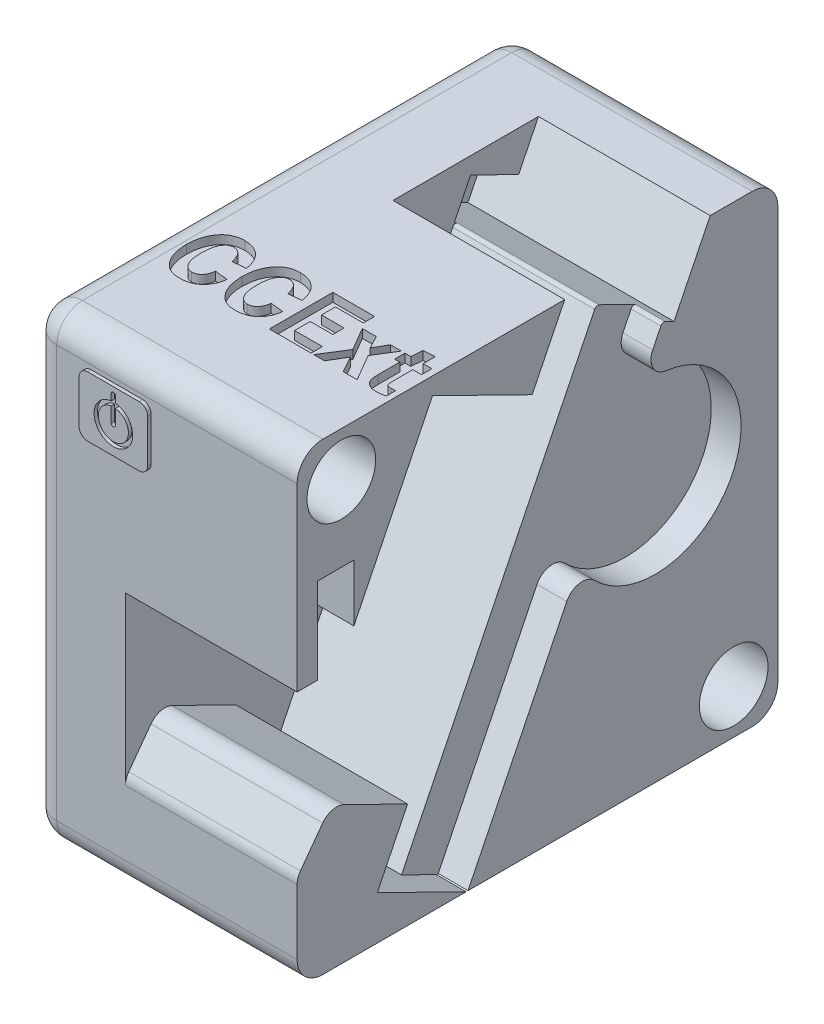
SolidWorks part; units mm, degrees
material "ABS"
ref_plane "Front" through (0, 0, 0) normal (0, 0, 1) x (1, 0, 0)
ref_plane "Top" through (0, 0, 0) normal (0, 1, 0) x (1, 0, 0)
ref_plane "Right" through (0, 0, 0) normal (1, 0, 0) x (0, 0, -1)
sketch "Sketch1" plane through (0, 0, 0) normal (0, 0, 1) x (1, 0, 0)
  line L0 (133.4483, 300.2587) -> (667.2416, 300.2587) construction
  line L2 (-196.85, 342.9) -> (196.85, 342.9)
  line L3 (-196.85, 342.9) -> (-196.85, 0)
  line L4 (-196.85, 0) -> (196.85, 0)
  line L5 (196.85, 342.9) -> (196.85, 0)
  dimension "D1" = 342.9
  dimension "D2" = 393.7
extrude "Boss-Extrude1" add sketch "Sketch1" along normal blind 355.6
sketch "Sketch2" plane through (0, 0, 355.6) normal (0, 0, 1) x (1, 0, 0)
  line L0 (196.85, 342.9) -> (-196.85, 342.9) construction
  line L1 (-158.75, 320.675) -> (-107.95, 320.675)
  line L2 (-158.75, 320.675) -> (-158.75, 276.225)
  line L3 (-158.75, 276.225) -> (-107.95, 276.225)
  line L4 (-107.95, 320.675) -> (-107.95, 276.225)
  line L5 (-158.75, 320.675) -> (-107.95, 276.225) construction
  line L6 (-158.75, 276.225) -> (-107.95, 320.675) construction
  line L7 (-196.85, 342.9) -> (-196.85, 0) construction
  point P0 (-133.35, 298.45)
  dimension "D1" = 44.45
  dimension "D2" = 63.5
  dimension "D3" = 44.45
  dimension "D4" = 50.8
extrude "Boss-Extrude2" add sketch "Sketch2" along normal blind 2.54
sketch "Sketch3" plane through (0, 0, 355.6) normal (0, 0, 1) x (1, 0, 0)
  line L0 (88.9, 298.45) -> (165.1, 298.45) construction
  line L1 (88.9, 307.975) -> (165.1, 307.975)
  line L2 (88.9, 288.925) -> (165.1, 288.925)
  line L5 (-107.95, 298.45) -> (88.9, 298.45) construction
  line L7 (-107.95, 276.225) -> (-107.95, 320.675) construction
  line L8 (196.85, 0) -> (196.85, 342.9) construction
  arc A0 (88.9, 307.975) -> (88.9, 288.925) centre (88.9, 298.45) ccw
  arc A1 (165.1, 288.925) -> (165.1, 307.975) centre (165.1, 298.45) ccw
  point P2 (127, 298.45)
  dimension "D1" = 19.05
  dimension "D2" = 76.2
  dimension "D3" = 31.75
extrude "Boss-Extrude3" add sketch "Sketch3" along normal blind 2.54
sketch "Sketch4" plane through (0, 0, 358.14) normal (0, 0, 1) x (1, 0, 0)
  line L0 (79.375, 298.45) -> (174.625, 298.45) construction
  arc A0 (88.9, 307.975) -> (88.9, 288.925) centre (88.9, 298.45) ccw construction
  arc A1 (165.1, 288.925) -> (165.1, 307.975) centre (165.1, 298.45) ccw construction
  circle A2 centre (92.075, 298.45) radius 3.81
  circle A3 centre (108.2865, 298.45) radius 3.81
  circle A4 centre (124.4979, 298.45) radius 3.81
  dimension "D1" = 7.62
  dimension "D2" = 16.2115
  dimension "D3" = 16.2115
  dimension "D4" = 12.7
extrude "Cut-Extrude1" cut sketch "Sketch4" against normal blind 2.54
sketch "Sketch5" plane through (0, 0, 355.6) normal (0, 0, 1) x (1, 0, 0)
  line L0 (-114.3, 177.8) -> (114.3, 177.8) construction
  line L1 (-114.3, 190.5) -> (114.3, 190.5)
  line L2 (-114.3, 165.1) -> (114.3, 165.1)
  line L3 (0, 177.8) -> (0, 342.9) construction
  line L4 (196.85, 342.9) -> (-196.85, 342.9) construction
  arc A0 (-114.3, 190.5) -> (-114.3, 165.1) centre (-114.3, 177.8) ccw
  arc A1 (114.3, 165.1) -> (114.3, 190.5) centre (114.3, 177.8) ccw
  point P2 (0, 177.8)
  dimension "D1" = 228.6
  dimension "D2" = 25.4
  dimension "D3" = 165.1
extrude "Boss-Extrude4" add sketch "Sketch5" along normal blind 50.8
fillet "Fillet1" radius 6.35 4 edges at (127, 177.8, 406.4) (0, 165.1, 406.4) (-127, 177.8, 406.4) (0, 190.5, 406.4)
fillet "Fillet2" radius 6.35 4 edges at (-158.75, 276.225, 356.87) (-107.95, 276.225, 356.87) (-107.95, 320.675, 356.87) (-158.75, 320.675, 356.87)
sketch "Sketch6" plane through (0, 0, 358.14) normal (0, 0, 1) x (1, 0, 0)
  line L0 (-133.35, 296.545) -> (-133.35, 276.225) construction
  line L3 (-133.35, 296.545) -> (-133.35, 315.595) construction
  line L4 (-134.9375, 296.545) -> (-134.9375, 315.595)
  line L5 (-131.7625, 296.545) -> (-131.7625, 315.595)
  line L6 (-152.4, 276.225) -> (-114.3, 276.225) construction
  circle A1 centre (-133.35, 296.545) radius 11.1125
  circle A2 centre (-133.35, 296.545) radius 14.2875
  arc A3 (-134.9375, 296.545) -> (-131.7625, 296.545) centre (-133.35, 296.545) ccw
  arc A4 (-131.7625, 315.595) -> (-134.9375, 315.595) centre (-133.35, 315.595) ccw
  point P12 (-133.35, 306.07)
  dimension "D2" = 22.225
  dimension "D3" = 3.175
  dimension "D4" = 19.05
  dimension "D5" = 20.32
  dimension "D1" = 3.175
extrude "Cut-Extrude2" cut sketch "Sketch6" against normal blind 2.54 contours L4 A2 L5 A1 | L5 A4 L4 A2 | L5 A2 L4 A1 | L4 A3 L5 A1 region at (-133.35, 301.4538, 358.14) region at (-140.889, 287.8397, 358.14) region at (-133.35, 309.2112, 358.14) region at (-133.35, 313.8328, 358.14)
fillet "Fillet3" radius 19.05 12 edges at (-196.85, 171.45, 0) (-196.85, 171.45, 355.6) (196.85, 171.45, 0) (196.85, 171.45, 355.6) (0, 0, 0) (0, 0, 355.6) (0, 342.9, 0) (0, 342.9, 355.6) (-196.85, 342.9, 177.8) (196.85, 0, 177.8) (-196.85, 0, 177.8) (196.85, 342.9, 177.8)
sketch "Sketch7" plane through (0, 0, 0) normal (1, 0, 0) x (0, 0, -1)
  line L0 (-51.7276, 342.9) -> (10.6627, 469.9)
  line L1 (-336.55, 342.9) -> (-19.05, 342.9) construction
  line L2 (-94.1768, 342.9) -> (-31.7865, 469.9)
  line L3 (-31.7865, 469.9) -> (10.6627, 469.9)
  line L4 (-94.1768, 342.9) -> (-51.7276, 342.9)
  line L5 (0, 323.85) -> (0, 19.05) construction
  dimension "D1" = 38.1
  dimension "D2" = 127
  dimension "D3" = 94.1768
  dimension "D4" = 63.837
extrude "Boss-Extrude5" add sketch "Sketch7" along normal mid plane 254
fillet "Fillet4" radius 39.116 2 edges at (-127, 469.9, 10.5619) (127, 469.9, 10.5619)
sketch "Sketch8" plane through (0, 342.9, 0) normal (0, 1, 0) x (1, 0, 0)
  line L0 (0, -94.1768) -> (0, -125.9268) construction
  line L1 (127, -94.1768) -> (-127, -94.1768) construction
  line L3 (-127, -157.6768) -> (127, -157.6768)
  line L4 (-127, -157.6768) -> (-127, -94.1768)
  line L5 (-127, -94.1768) -> (127, -94.1768)
  line L6 (127, -157.6768) -> (127, -94.1768)
  line L7 (-127, -157.6768) -> (127, -94.1768) construction
  line L8 (-127, -94.1768) -> (127, -157.6768) construction
  dimension "D1" = 63.5
  dimension "D2" = 254
extrude "Cut-Extrude3" cut sketch "Sketch8" against normal blind 25.4
sketch "Sketch9" plane through (0, 0, 0) normal (1, 0, 0) x (0, 0, -1)
  line L1 (-912.7094, 769.4471) -> (-210.006, -1175.153)
  line L2 (-210.006, -1175.153) -> (1122.7154, 405.706)
  line L3 (1122.7154, 405.706) -> (-912.7094, 769.4471)
  circle A0 centre (0, 0) radius 596.8851 construction
extrude "Cut-Extrude4" cut sketch "Sketch9" along normal through all
sketch "Sketch10" plane through (0, 0, 0) normal (1, 0, 0) x (0, 0, -1)
  line L0 (-94.1768, 342.9) -> (-256.3917, 12.7)
  line L1 (-157.6768, 342.9) -> (-181.7103, 293.9781)
  line L2 (-31.7865, 469.9) -> (-94.1768, 342.9) construction
  line L3 (-336.55, 165.1) -> (-255.4426, 330.2)
  line L5 (-355.6, 19.05) -> (-355.6, 165.1) construction
  line L9 (-157.6768, 342.9) -> (-94.1768, 342.9)
  line L14 (-255.4426, 330.2) -> (-181.7103, 293.9781)
  line L15 (-336.55, 0) -> (-19.05, 0) construction
  line L16 (-157.6768, 342.9) -> (-336.55, 342.9) construction
  line L17 (-341.781, 111.2476) -> (-273.8883, 77.8944)
  line L19 (-256.3917, 12.7) -> (-296.2874, 32.2993)
  line L20 (-296.2874, 32.2993) -> (-273.8883, 77.8944)
  line L21 (-336.55, 165.1) -> (-355.6, 165.1)
  line L22 (-355.6, 165.1) -> (-355.6, 83.1181)
  line L23 (-238.3444, 321.8003) -> (-409.5147, -26.6293) construction
  line L24 (-341.781, 111.2476) -> (-355.6, 83.1181)
  dimension "D1" = 12.7
  dimension "D2" = 12.7
  dimension "D3" = 50.8
  dimension "D4" = 44.45
  dimension "D5" = 19.05
  dimension "D6" = 19.05
extrude "Cut-Extrude5" cut sketch "Sketch10" against normal blind 127
sketch "Sketch11" plane through (0, 0, 0) normal (1, 0, 0) x (0, 0, -1)
  line L0 (-94.1768, 342.9) -> (-106.6549, 317.5)
  line L1 (-106.6549, 317.5) -> (-94.1768, 317.5)
  line L2 (-94.1768, 317.5) -> (-94.1768, 342.9)
extrude "Boss-Extrude6" add sketch "Sketch11" against normal up to surface (127 mm away) up to face at (-127, 199.4183, 238.9182)
sketch "Sketch12" plane through (0, 103.9367, 211.5706) normal (0, 0.4409, 0.8975) x (1, 0, 0)
  line L0 (-127, -101.6517) -> (0, -101.6517) construction
  line L1 (0, 426.4566) -> (-22, 426.4566)
  line L2 (0, 426.4566) -> (0, -101.6517)
  line L3 (0, -101.6517) -> (-22, -101.6517)
  line L4 (-22, 426.4566) -> (-22, -101.6517)
  dimension "D1" = 22
extrude "Cut-Extrude6" cut sketch "Sketch12" against normal blind 30
sketch "Sketch13" plane through (0, 0, 0) normal (1, 0, 0) x (0, 0, -1)
  line L0 (-90.7362, 196.8695) -> (0, 196.8695) construction
  line L1 (0, 19.05) -> (0, 323.85) construction
  line L2 (-90.7362, 196.8695) -> (-90.7362, 0) construction
  line L3 (-336.55, 0) -> (-230.5399, 0) construction
  circle A0 centre (-90.7362, 196.8695) radius 63.5
  dimension "D3" = 127
  dimension "D1" = 196.8695
  dimension "D2" = 90.7362
extrude "Cut-Extrude7" cut sketch "Sketch13" against normal up to surface (22 mm away) up to face at (-22, 190.5, 149.2572)
fillet "Fillet5" radius 12.7 2 edges at (-11, 259.4033, 101.771) (-11, 167.3852, 146.9761)
sketch "Sketch14" plane through (0, 0, 0) normal (1, 0, 0) x (0, 0, -1)
  line L0 (-400.05, 165.1) -> (-336.55, 165.1) construction
  line L1 (-255.4426, 330.2) -> (-336.55, 165.1) construction
  line L2 (-255.4426, 330.2) -> (-336.55, 165.1) construction
  line L3 (-355.5357, 165.1) -> (-336.55, 165.1)
  line L4 (-336.55, 165.1) -> (-328.1786, 182.1405)
  arc A0 (-355.5357, 165.1) -> (-328.1786, 182.1405) centre (-355.5357, 195.58) ccw
  dimension "D1" = 30.48
extrude "Cut-Extrude8" cut sketch "Sketch14" against normal up to surface (127 mm away) up to face at (-127, 177.9489, 264.1005)
sketch "Sketch15" plane through (0, 0, 0) normal (1, 0, 0) x (0, 0, -1)
  circle A0 centre (-322.9044, 310.2044) radius 25.4
  circle A1 centre (-32.6956, 32.6956) radius 25.4
  dimension "D1" = 50.8
  dimension "D2" = 50.8
extrude "Cut-Extrude9" cut sketch "Sketch15" against normal blind 53.34
sketch "Sketch16" plane through (0, 342.9, 0) normal (0, 1, 0) x (1, 0, 0)
  line L0 (-177.8, -336.55) -> (-177.8, -285.75) construction
  text T0 "CCExtractor" font "Franklin Gothic Medium" height in points 190
  dimension "D1" = 50.8
extrude "Cut-Extrude10" cut sketch "Sketch16" against normal blind 6.35
fillet "Fillet6" radius 12.7 1 edges at (-63.5, 111.2476, 341.781)
fillet "Fillet7" radius 50.8 1 edges at (-63.5, 83.1181, 355.6)
sketch "Sketch17" plane through (0, 0, 0) normal (1, 0, 0) x (0, 0, -1)
  line L0 (-315.6, 207.7452) -> (-315.6, 254)
  line L1 (-315.6, 254) -> (-340.6, 254)
  line L2 (-340.6, 254) -> (-340.6, 190.5)
  line L3 (-340.6, 190.5) -> (-355.6, 190.5)
  line L8 (-328.1786, 182.1405) -> (-255.4426, 330.2)
  line L9 (-255.4426, 330.2) -> (-181.7103, 293.9781)
  line L10 (-181.7103, 293.9781) -> (-157.6768, 342.9)
  line L11 (-157.6768, 342.9) -> (-336.55, 342.9)
  line L12 (-355.6, 323.85) -> (-355.6, 190.5)
  line L13 (-355.6, 190.5) -> (-400.05, 190.5)
  line L14 (-406.4, 184.15) -> (-406.4, 171.45)
  line L15 (-400.05, 165.1) -> (-355.5357, 165.1)
  line L16 (-328.1786, 182.1405) -> (-315.6, 207.7452)
  line L21 (-355.6, 190.5) -> (-400.05, 190.5)
  line L22 (-406.4, 184.15) -> (-406.4, 171.45)
  line L23 (-400.05, 165.1) -> (-355.5357, 165.1)
  arc A4 (-355.5357, 165.1) -> (-328.1786, 182.1405) centre (-355.5357, 195.58) ccw
  arc A5 (-336.55, 342.9) -> (-355.6, 323.85) centre (-336.55, 323.85) ccw
  arc A6 (-400.05, 190.5) -> (-406.4, 184.15) centre (-400.05, 184.15) ccw
  arc A7 (-406.4, 171.45) -> (-400.05, 165.1) centre (-400.05, 171.45) ccw
  arc A8 (-355.5357, 165.1) -> (-328.1786, 182.1405) centre (-355.5357, 195.58) ccw
  arc A10 (-400.05, 190.5) -> (-406.4, 184.15) centre (-400.05, 184.15) ccw
  arc A11 (-406.4, 171.45) -> (-400.05, 165.1) centre (-400.05, 171.45) ccw
  dimension "D2" = 15
  dimension "D3" = 25
  dimension "D4" = 63.5
  dimension "D1" = 0
extrude "Cut-Extrude11" cut sketch "Sketch17" against normal up to surface (127 mm away) up to face at (-127, 165.4031, 281.3354)
sketch "Sketch18" plane through (-127, 0, 0) normal (1, 0, 0) x (0, 0, -1)
  line L0 (-315.6, 207.7452) -> (-315.6, 254) construction
  line L1 (-340.6, 254) -> (-315.6, 254)
  line L2 (-340.6, 254) -> (-340.6, 234)
  line L3 (-340.6, 234) -> (-315.6, 234)
  line L4 (-315.6, 254) -> (-315.6, 234)
  dimension "D1" = 20
extrude "Cut-Extrude12" cut sketch "Sketch18" against normal blind 25.4
sketch "Sketch19" plane through (0, 0, 0) normal (1, 0, 0) x (0, 0, -1)
  line L0 (-313.6, 211.8164) -> (-315.6, 207.7452)
  line L1 (-255.4426, 330.2) -> (-315.6, 207.7452) construction
  line L2 (-315.6, 207.7452) -> (-315.6, 254)
  line L3 (-315.6, 254) -> (-313.6, 254)
  line L4 (-313.6, 254) -> (-313.6, 211.8164)
  dimension "D1" = 2
extrude "Cut-Extrude13" cut sketch "Sketch19" against normal up to surface (127 mm away) up to face at (-127, 178.9975, 285.6136)
sketch "Sketch20" plane through (-127, 0, 0) normal (1, 0, 0) x (0, 0, -1)
  line L0 (-313.6, 211.8164) -> (-313.6, 254) construction
  line L1 (-313.6, 232) -> (-340.6, 232)
  line L2 (-313.6, 232) -> (-313.6, 254)
  line L3 (-313.6, 254) -> (-340.6, 254)
  line L4 (-340.6, 232) -> (-340.6, 254)
  line L5 (-340.6, 234) -> (-315.6, 234) construction
  dimension "D1" = 2
extrude "Cut-Extrude14" cut sketch "Sketch20" against normal blind 25.4
sketch "Sketch21" plane through (0, 0, 0) normal (1, 0, 0) x (0, 0, -1)
  line L0 (-94.1768, 342.9) -> (-112.3576, 305.8917)
  line L1 (-256.3917, 12.7) -> (-94.1768, 342.9) construction
  line L2 (-112.3576, 305.8917) -> (-85.4314, 292.6639)
  line L3 (1.6381, 469.9) -> (-92.6006, 278.0704) construction
  line L4 (-85.4314, 292.6639) -> (-78.1613, 289.0923)
  line L5 (-78.1613, 289.0923) -> (-51.7276, 342.9)
  line L6 (-51.7276, 342.9) -> (10.6627, 469.9) construction
  line L7 (-19.05, 342.9) -> (-51.7276, 342.9) construction
  line L8 (-94.1768, 342.9) -> (-31.7865, 469.9)
  line L9 (-31.7865, 469.9) -> (10.6627, 469.9)
  line L10 (10.6627, 469.9) -> (-51.7276, 342.9)
extrude "Cut-Extrude16" cut sketch "Sketch21" against normal up to surface (127 mm away) up to face at (-127, 179.0019, 285.3636)
sketch "Sketch22" plane through (-127, 0, 0) normal (1, 0, 0) x (0, 0, -1)
  line L0 (-78.1613, 289.0923) -> (-112.3576, 305.8917)
  line L1 (-78.1613, 289.0923) -> (-66.0798, 313.685)
  line L2 (-112.3576, 305.8917) -> (-100.2762, 330.4844)
  line L3 (-66.0798, 313.685) -> (-100.2762, 330.4844)
  dimension "D1" = 27.4
extrude "Cut-Extrude17" cut sketch "Sketch22" against normal blind 25.4
sketch "Sketch23" plane through (0, 0, 0) normal (1, 0, 0) x (0, 0, -1)
  line L0 (-78.1613, 289.0923) -> (-76.815, 288.4309)
  line L1 (-76.815, 288.4309) -> (-50.0564, 342.9)
  line L2 (-19.05, 342.9) -> (-51.7276, 342.9) construction
  line L3 (-50.0564, 342.9) -> (-51.7276, 342.9)
  line L4 (-51.7276, 342.9) -> (-78.1613, 289.0923)
  line L5 (-112.3576, 305.8917) -> (-78.1613, 289.0923) construction
  dimension "D1" = 1.5
extrude "Cut-Extrude18" cut sketch "Sketch23" against normal up to surface (127 mm away) up to face at (-127, 200.7417, 252.7411)
sketch "Sketch24" plane through (-127, 0, 0) normal (1, 0, 0) x (0, 0, -1)
  line L0 (-78.1613, 289.0923) -> (-76.815, 288.4309)
  line L1 (-78.1613, 289.0923) -> (-66.0798, 313.685)
  line L2 (-76.815, 288.4309) -> (-64.7335, 313.0236)
  line L3 (-66.0798, 313.685) -> (-64.7335, 313.0236)
extrude "Cut-Extrude19" cut sketch "Sketch24" against normal up to surface (25.4 mm away) up to face at (-152.4, 309.7884, 89.2187)
fillet "Fillet8" radius 2.54 1 edges at (-11, 292.6639, 85.4314)
fillet "Fillet9" radius 2.54 1 edges at (-74.5, 305.8917, 112.3576)
sketch "Sketch25" plane through (0, 0, 0) normal (1, 0, 0) x (0, 0, -1)
  line L0 (-330.3822, 105.6478) -> (-355.6, 71.3138)
  line L4 (-347.3808, 99.8488) -> (-350.3951, 93.713)
  line L5 (-347.3808, 99.8488) -> (-350.3951, 93.713)
  arc A6 (-350.3951, 93.713) -> (-355.6, 71.3138) centre (-304.8, 71.3138) ccw
  arc A7 (-330.3822, 105.6478) -> (-347.3808, 99.8488) centre (-335.982, 94.249) ccw
  arc A8 (-350.3951, 93.713) -> (-355.6, 71.3138) centre (-304.8, 71.3138) ccw
  arc A9 (-330.3822, 105.6478) -> (-347.3808, 99.8488) centre (-335.982, 94.249) ccw
  dimension "D1" = 0
extrude "Cut-Extrude20" cut sketch "Sketch25" against normal up to surface (127 mm away) up to face at (-127, 210.5961, 239.1838)
fillet "Fillet10" radius 12.7 2 edges at (-63.5, 71.3138, 355.6) (-63.5, 105.6478, 330.3822)
equation "\"D3@Sketch4\"=\"D2@Sketch4\""
